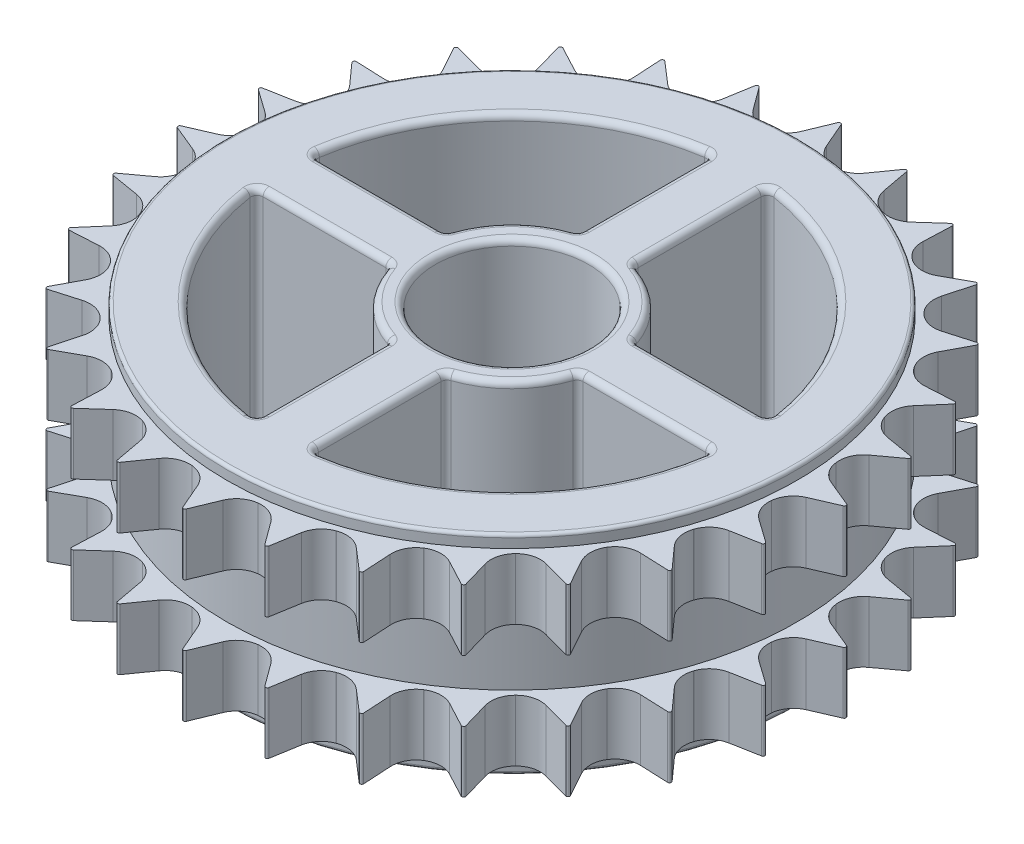
SolidWorks part; units mm, degrees
ref_plane "Front Plane" through (0, 0, 0) normal (0, 0, 1) x (1, 0, 0)
ref_plane "Top Plane" through (0, 0, 0) normal (0, 1, 0) x (1, 0, 0)
ref_plane "Right Plane" through (0, 0, 0) normal (1, 0, 0) x (0, 0, -1)
sketch "Sketch1" plane through (0, 0, 0) normal (0, 1, 0) x (1, 0, 0)
  line L0 (3, 47.4052) -> (0, 54.5)
  line L1 (0, 54.5) -> (-3, 47.4052)
  line L2 (0, 54.5) -> (0, 47.5) construction
  line L3 (-3, 47.4052) -> (0, 47.5) construction
  line L4 (0, 47.5) -> (3, 47.4052) construction
  line L5 (-3, 47.4052) -> (0, 47.5) construction
  line L6 (0, 47.5) -> (3, 47.4052) construction
  line L7 (13.8515, 45.4355) -> (12.5686, 53.0309)
  line L8 (12.5686, 53.0309) -> (8.0132, 46.8192)
  line L9 (23.9563, 41.0164) -> (24.4596, 48.703)
  line L10 (24.4596, 48.703) -> (18.5945, 43.7092)
  line L11 (32.7696, 34.3861) -> (35.0319, 41.7494)
  line L12 (35.0319, 41.7494) -> (28.1733, 38.2428)
  line L13 (39.8163, 25.902) -> (43.7157, 32.5451)
  line L14 (43.7157, 32.5451) -> (36.2333, 30.7148)
  line L15 (44.7164, 16.0216) -> (50.0428, 21.5863)
  line L16 (50.0428, 21.5863) -> (42.3399, 21.5309)
  line L17 (47.2059, 5.2774) -> (53.672, 9.4638)
  line L18 (53.672, 9.4638) -> (46.164, 11.1862)
  line L19 (47.1505, -5.7513) -> (54.4078, -3.1689)
  line L20 (54.4078, -3.1689) -> (47.4994, 0.2386)
  line L21 (44.5532, -16.4699) -> (52.2104, -15.6308)
  line L22 (52.2104, -15.6308) -> (46.2741, -10.722)
  line L23 (39.5541, -26.3007) -> (47.1984, -27.25)
  line L24 (47.1984, -27.25) -> (42.5541, -21.1045)
  line L25 (32.4225, -34.7135) -> (39.6419, -37.4002)
  line L26 (39.6419, -37.4002) -> (36.54, -30.3493)
  line L27 (23.5431, -41.255) -> (29.9482, -45.5341)
  line L28 (29.9482, -45.5341) -> (28.556, -37.9579)
  line L29 (13.3944, -45.5723) -> (18.6401, -51.2132)
  line L30 (18.6401, -51.2132) -> (19.0326, -43.5202)
  line L31 (2.5237, -47.4329) -> (6.3271, -54.1315)
  line L32 (6.3271, -54.1315) -> (8.4831, -46.7364)
  line L33 (-8.4831, -46.7364) -> (-6.3271, -54.1315)
  line L34 (-6.3271, -54.1315) -> (-2.5237, -47.4329)
  line L35 (-19.0326, -43.5202) -> (-18.6401, -51.2132)
  line L36 (-18.6401, -51.2132) -> (-13.3944, -45.5723)
  line L37 (-28.556, -37.9579) -> (-29.9482, -45.5341)
  line L38 (-29.9482, -45.5341) -> (-23.5431, -41.255)
  line L39 (-36.54, -30.3493) -> (-39.6419, -37.4002)
  line L40 (-39.6419, -37.4002) -> (-32.4225, -34.7135)
  line L41 (-42.5541, -21.1045) -> (-47.1984, -27.25)
  line L42 (-47.1984, -27.25) -> (-39.5541, -26.3007)
  line L43 (-46.2741, -10.722) -> (-52.2104, -15.6308)
  line L44 (-52.2104, -15.6308) -> (-44.5532, -16.4699)
  line L45 (-47.4994, 0.2386) -> (-54.4078, -3.1689)
  line L46 (-54.4078, -3.1689) -> (-47.1505, -5.7513)
  line L47 (-46.164, 11.1862) -> (-53.672, 9.4638)
  line L48 (-53.672, 9.4638) -> (-47.2059, 5.2774)
  line L49 (-42.3399, 21.5309) -> (-50.0428, 21.5863)
  line L50 (-50.0428, 21.5863) -> (-44.7164, 16.0216)
  line L51 (-36.2333, 30.7148) -> (-43.7157, 32.5451)
  line L52 (-43.7157, 32.5451) -> (-39.8163, 25.902)
  line L53 (-28.1733, 38.2428) -> (-35.0319, 41.7494)
  line L54 (-35.0319, 41.7494) -> (-32.7696, 34.3861)
  line L55 (-18.5945, 43.7092) -> (-24.4596, 48.703)
  line L56 (-24.4596, 48.703) -> (-23.9563, 41.0164)
  line L57 (-8.0132, 46.8192) -> (-12.5686, 53.0309)
  line L58 (-12.5686, 53.0309) -> (-13.8515, 45.4355)
  line L59 (0, 16) -> (0, 37.5) construction
  line L60 (-4.5, 37.229) -> (-4.5, 15.3542)
  line L61 (4.5, 37.229) -> (4.5, 15.3542)
  line L62 (37.229, -4.5) -> (15.3542, -4.5)
  line L63 (37.229, 4.5) -> (15.3542, 4.5)
  line L64 (-4.5, -37.229) -> (-4.5, -15.3542)
  line L65 (4.5, -37.229) -> (4.5, -15.3542)
  line L66 (-37.229, 4.5) -> (-15.3542, 4.5)
  line L67 (-37.229, -4.5) -> (-15.3542, -4.5)
  line L69 (-1.7, 1.3964) -> (-1.7, -1.3964)
  circle A0 centre (0, 0) radius 47.5
  circle A1 centre (0, 0) radius 37.5
  circle A2 centre (0, 0) radius 5
  circle A3 centre (0, 0) radius 2.2
  circle A4 centre (0, 0) radius 16
  circle A5 centre (0, 0) radius 46.5
  point P88 (0, 0)
  point P111 (0, 0)
  dimension "D1" = 95
  dimension "D5" = 75
  dimension "D6" = 10
  dimension "D7" = 4.4
  dimension "D8" = 32
  dimension "D9" = 4
  dimension "D11" = 0.5
  dimension "D12" = 1
  dimension "D2" = 7
  dimension "D3" = 3
  dimension "D10" = 9
  dimension "D4" = 27
extrude "Boss-Extrude2" add sketch "Sketch1" along normal blind 10 from offset 2 contours A2 A3 | L69 A3 | A4 A2 | A4 L62 A1 L63 | A4 L64 A1 L65 | A4 L66 A1 L67 | A4 L61 A1 L60 | A5 A1 | A0 | L69 A3 region at (5.4988, 0, -47.0454) region at (0, 0, -26.5974) region at (0, 0, -15.5475) region at (-26.5974, 0, 0) region at (26.5974, 0, 0) region at (0, 0, 26.5974) region at (0.1274, 0, 0) region at (-1.9021, 0, 0) region at (-4.8586, 0, 0) region at (-45.1848, 0, 0)
extrude "Boss-Extrude3" add sketch "Sketch1<7>" along normal blind 22 contours L69 A3 | A5 A1 | A4 A2 | A2 A3 | A4 L66 A1 L67 | A4 L64 A1 L65 | A4 L62 A1 L63 | A4 L61 A1 L60 | A3 region at (0, 0, -26.5974) region at (0, 0, -15.5475) region at (-26.5974, 0, 0) region at (26.5974, 0, 0) region at (0, 0, 26.5974) region at (-1.9021, 0, 0) region at (-4.8586, 0, 0) region at (-45.1848, 0, 0)
sketch "Sketch1<7>" plane through (0, 0, 0) normal (0, 1, 0) x (1, 0, 0) same geometry as "Sketch1"
extrude "Boss-Extrude4" add sketch "Sketch1<8>" along normal blind 10 from surface contours A4 A2 | A2 A3 | L69 A3 | A4 L62 A1 L63 | A4 L64 A1 L65 | A4 L66 A1 L67 | A4 L61 A1 L60 | A5 A1 | A0 region at (5.4988, 0, -47.0454) region at (0, 0, -26.5974) region at (0, 0, -15.5475) region at (-26.5974, 0, 0) region at (26.5974, 0, 0) region at (0, 0, 26.5974) region at (-1.9021, 0, 0) region at (-4.8586, 0, 0) region at (-45.1848, 0, 0) starting at face at (-17.1554, 22, 17.1554)
sketch "Sketch1<8>" plane through (0, 0, 0) normal (0, 1, 0) x (1, 0, 0) same geometry as "Sketch1"
extrude "Boss-Extrude6" add sketch "Sketch1<10>" along normal blind 10 from offset 2 contours A0 L57 L58 region at (-11.4875, 0, -48.4696)
sketch "Sketch1<10>" plane through (0, 0, 0) normal (0, 1, 0) x (1, 0, 0) same geometry as "Sketch1"
extrude "Boss-Extrude7" add sketch "Sketch1<12>" along normal blind 10 from surface contours A0 L57 L58 region at (-11.4875, 0, -48.4696) starting at face at (0, 22, 47.5)
sketch "Sketch1<12>" plane through (0, 0, 0) normal (0, 1, 0) x (1, 0, 0) same geometry as "Sketch1"
fillet "Fillet1" radius 4 4 edges at (-13.8515, 7, -45.4355) (-8.0132, 7, -46.8192) (-13.8515, 27, -45.4355) (-8.0132, 27, -46.8192)
fillet "Fillet2" radius 0.3 2 edges at (-12.5686, 7, -53.0309) (-12.5686, 27, -53.0309)
pattern_circular "CirPattern1" count 28 over 360 about axis through (0, 32, 0) along (0, 1, 0) of "Fillet2", "Fillet1", "Boss-Extrude7", "Boss-Extrude6"
sketch "Sketch3" plane through (0, 32, 0) normal (0, 1, 0) x (1, 0, 0)
  circle A0 centre (0, 0) radius 2.5
sketch "Sketch4" plane through (0, 32, 0) normal (0, 1, 0) x (1, 0, 0)
  circle A0 centre (0, 0) radius 0.5
  dimension "D1" = 1
sketch "Sketch6" plane through (0, 32, 0) normal (0, 1, 0) x (1, 0, 0)
  line L0 (-15.3542, 4.5) -> (-37.229, 4.5)
  line L1 (-15.3542, -4.5) -> (-37.229, -4.5)
  line L2 (4.5, 15.3542) -> (4.5, 37.229)
  line L3 (-4.5, 15.3542) -> (-4.5, 37.229)
  line L4 (15.3542, -4.5) -> (37.229, -4.5)
  line L5 (15.3542, 4.5) -> (37.229, 4.5)
  line L6 (-4.5, -15.3542) -> (-4.5, -37.229)
  line L7 (4.5, -15.3542) -> (4.5, -37.229)
  circle A0 centre (0, 0) radius 16
  circle A1 centre (0, 0) radius 46.5
  circle A2 centre (0, 0) radius 37.5
  circle A3 centre (0, 0) radius 16
  circle A4 centre (0, 0) radius 16
  circle A5 centre (0, 0) radius 16
  point P31 (0, 0)
  dimension "D1" = 93
  dimension "D2" = 32
  dimension "D3" = 4
extrude "Boss-Extrude12" add sketch "Sketch6" along normal blind 2 contours L2 A2 L3 A0 | A1 A2 | L0 A2 L1 A0 | L6 A2 L7 A0 | A0 | L4 A2 L5 A0 region at (-26.5974, 32, 0) region at (0, 32, 0) region at (0, 32, -26.5974) region at (0, 32, 26.5974) region at (26.5974, 32, 0) region at (-45.1848, 32, 0)
fillet "Fillet9" radius 0.5 2 edges at (0, 34, 46.5) (0, 0, 46.5)
sketch "Sketch7" plane through (0, 34, 0) normal (0, 1, 0) x (1, 0, 0)
  line L0 (0, 0) -> (0, 5.8384) construction
  line L1 (0, 0) -> (-4.8311, 0) construction
  circle A1 centre (-8, 0) radius 1.5
  circle A2 centre (0, 8) radius 1.5
  circle A3 centre (8, 0) radius 1.5
  circle A4 centre (0, -8) radius 1.5
  point P18 (0, 0)
  dimension "D2" = 3
  dimension "D1" = 90
  dimension "D3" = 8
  dimension "D4" = 4
extrude "Cut-Extrude1" cut sketch "Sketch7" against normal up to next
sketch "Sketch10" plane through (0, 34, 0) normal (0, 1, 0) x (1, 0, 0)
  circle A0 centre (0, 0) radius 12.5
  dimension "D1" = 25
extrude "Cut-Extrude2" cut sketch "Sketch10" against normal offset from surface (21 mm away) 13 up to face at (-8, 0, 1.5)
fillet "Fillet17" radius 1 49 edges at (15.3542, 17, -4.5) (37.229, 17, -4.5) (-4.5, 17, 37.229) (-4.5, 17, 15.3542) (-15.3542, 17, 4.5) (-37.229, 17, 4.5) (-37.229, 17, -4.5) (-15.3542, 17, -4.5) (-4.5, 17, -15.3542) (-4.5, 17, -37.229) (4.5, 17, -37.229) (4.5, 17, -15.3542) (4.5, 17, 15.3542) (4.5, 17, 37.229) (37.229, 17, 4.5) (15.3542, 17, 4.5) (-11.3137, 34, 11.3137) (-26.5165, 34, 26.5165) (-11.3137, 0, 11.3137) (-26.5165, 0, 26.5165) (-11.3137, 34, -11.3137) (-26.5165, 34, -26.5165) (-11.3137, 0, -11.3137) (-26.5165, 0, -26.5165) (11.3137, 34, -11.3137) (26.5165, 34, -26.5165) (26.5165, 0, -26.5165) (11.3137, 0, -11.3137) (11.3137, 34, 11.3137) (26.5165, 34, 26.5165) (26.5165, 0, 26.5165) (11.3137, 0, 11.3137) (26.2916, 34, -4.5) (26.2916, 0, -4.5) (-4.5, 34, 26.2916) (-4.5, 0, 26.2916) (-26.2916, 34, 4.5) (-26.2916, 0, 4.5) (-26.2916, 34, -4.5) (-26.2916, 0, -4.5) (-4.5, 34, -26.2916) (-4.5, 0, -26.2916) (4.5, 34, -26.2916) (4.5, 0, -26.2916) (4.5, 34, 26.2916) (4.5, 0, 26.2916) (26.2916, 34, 4.5) (26.2916, 0, 4.5) (0, 34, 12.5)
sketch "Sketch11" plane through (0, 0, 0) normal (0, 0, 1) x (1, 0, 0)
  line L0 (-49.6016, 12) -> (-53.8424, 12) construction
  line L1 (-53.8424, 2) -> (-49.6016, 2) construction
  line L2 (-49.6016, 2) -> (-49.6016, 12) construction
  line L3 (-53.8424, 12) -> (-54.0278, 12) construction
  line L4 (-53.847, 12) -> (-53.847, 2) construction
  line L5 (-54.0278, 2) -> (-53.8424, 2) construction
  line L6 (-53.8424, 32) -> (-54.0278, 32) construction
  line L7 (-53.847, 32) -> (-53.847, 22) construction
  line L8 (-54.0278, 22) -> (-53.8424, 22) construction
  line L9 (-49.6016, 32) -> (-53.8424, 32) construction
  line L10 (-53.8424, 22) -> (-49.6016, 22) construction
  line L11 (-49.6016, 22) -> (-49.6016, 32) construction
  line L13 (-49.6016, 12) -> (-53.8424, 12)
  line L14 (-53.8424, 2) -> (-49.6016, 2)
  line L15 (-49.6016, 2) -> (-49.6016, 12)
  line L16 (-53.8424, 12) -> (-54.0278, 12)
  line L17 (-53.847, 12) -> (-53.847, 2)
  line L18 (-54.0278, 2) -> (-53.8424, 2)
  line L19 (-53.8424, 32) -> (-53.9388, 32)
  line L20 (-53.847, 32) -> (-53.847, 22)
  line L21 (-54.0278, 22) -> (-53.8424, 22)
  line L22 (-49.6016, 32) -> (-53.8424, 32)
  line L23 (-53.8424, 22) -> (-49.6016, 22)
  line L24 (-49.6016, 22) -> (-49.6016, 32)
  line L25 (-53.9388, 32) -> (-54.0278, 22)
  line L26 (-54.0278, 12) -> (-54.0278, 2) construction
  line L27 (-54.0278, 12) -> (-54.0278, 2)
  line L28 (-54.0278, 22) -> (-54.0278, 12) construction
  line L29 (-53.9388, 17) -> (-47.598, 17) construction
  line L30 (-52.9995, 27) -> (-56.6207, 27) construction
  line L31 (-49.6016, 32) -> (-53.9477, 31)
  line L32 (-49.6016, 22) -> (-53.9477, 23)
  line L33 (-49.6016, 12) -> (-53.9477, 11)
  line L34 (-49.6016, 2) -> (-53.9477, 3)
  line L35 (0, 27) -> (0, 33.2542) construction
  line L36 (-53.9388, 32) -> (-54.2683, 32)
  line L37 (-53.9477, 31) -> (-54.2683, 31)
  line L38 (-53.9477, 31) -> (-53.9477, 23)
  line L39 (-53.9477, 23) -> (-54.2683, 23)
  line L40 (-54.2683, 31) -> (-54.2683, 23)
  line L41 (-54.2683, 32) -> (-54.2683, 31)
  line L42 (-54.2683, 23) -> (-54.2683, 22)
  line L43 (-54.2683, 22) -> (-54.0278, 22)
  line L45 (-54.0278, 12) -> (-54.2683, 12)
  line L46 (-54.0278, 12) -> (-54.0278, 2)
  line L47 (-54.0278, 2) -> (-54.2683, 2)
  line L48 (-54.2683, 12) -> (-54.2683, 2)
  point P7 (-54.0278, 17)
  point P20 (-53.9833, 27)
  dimension "D1" = 1
revolve "Cut-Revolve1" [suppressed] cut sketch "Sketch11" angle 360 about L35
